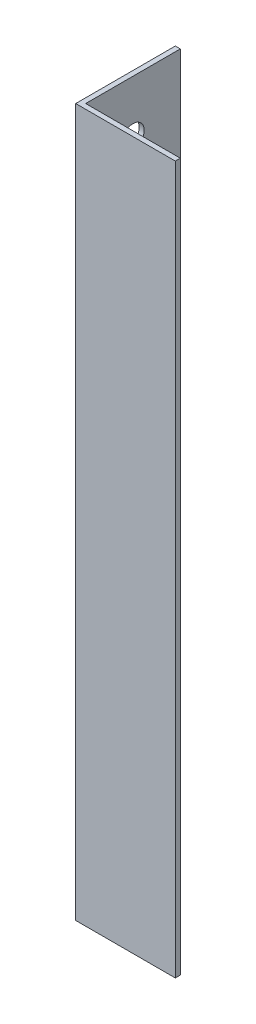
SolidWorks part; units mm, degrees
material "1060 Сплав"
ref_plane "Спереди" through (0, 0, 0) normal (0, 0, 1) x (1, 0, 0)
ref_plane "Сверху" through (0, 0, 0) normal (0, 1, 0) x (1, 0, 0)
ref_plane "Справа" through (0, 0, 0) normal (1, 0, 0) x (0, 0, -1)
sketch "Эскиз1" plane through (0, 0, 0) normal (0, 1, 0) x (1, 0, 0)
  line L0 (0, 0) -> (0, 20)
  line L1 (0, 20) -> (1, 20)
  line L2 (1, 20) -> (1, 1)
  line L3 (1, 1) -> (20, 1)
  line L4 (20, 1) -> (20, 0)
  line L5 (20, 0) -> (0, 0)
  dimension "D1" = 1
  dimension "D2" = 20
extrude "Бобышка-Вытянуть1" add sketch "Эскиз1" along normal blind 142
sketch "Эскиз2" plane through (1, 0, 0) normal (1, 0, 0) x (0, 0, -1)
  line L0 (10.5, 142) -> (10.5, 0) construction
  line L1 (1, 142) -> (20, 142) construction
  line L2 (1, 0) -> (20, 0) construction
  circle A0 centre (10.5, 131.5) radius 2.25
  dimension "D1" = 10.5
  dimension "D2" = 4.5
extrude "Вырез-Вытянуть1" cut sketch "Эскиз2" against normal through all
sketch "Эскиз3" plane through (0, 0, 0) normal (-1, 0, 0) x (0, 0, 1)
  circle A0 centre (-10.5, 30.5) radius 2.25 construction
  circle A1 centre (-10.5, 30.5) radius 2.25
extrude "Вырез-Вытянуть2" cut sketch "Эскиз3" against normal through all
